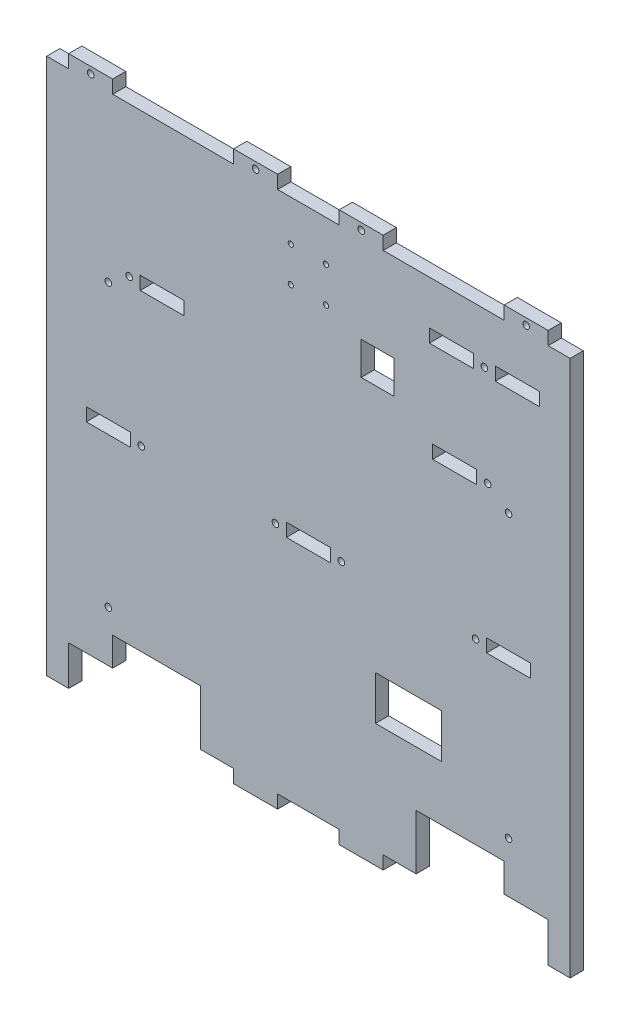
SolidWorks part; units mm, degrees
ref_plane "Plan de face" through (0, 0, 0) normal (0, 0, 1) x (1, 0, 0)
ref_plane "Plan de dessus" through (0, 0, 0) normal (0, 1, 0) x (1, 0, 0)
ref_plane "Plan de droite" through (0, 0, 0) normal (1, 0, 0) x (0, 0, -1)
sketch "Esquisse1" plane through (0, 0, 0) normal (0, 0, 1) x (1, 0, 0)
  line L0 (0, 139.6766) -> (0, -178.3461) construction
  line L1 (-109, 119) -> (109, 119)
  line L2 (-109, 119) -> (-109, -119)
  line L3 (-109, -119) -> (109, -119)
  line L4 (109, 119) -> (109, -119)
  line L5 (-101, -16) -> (-81, -16)
  line L6 (-101, -16) -> (-101, -10)
  line L7 (-101, -10) -> (-81, -10)
  line L8 (-81, -16) -> (-81, -10)
  line L9 (-10, -16) -> (10, -16)
  line L10 (-10, -16) -> (-10, -10)
  line L11 (-10, -10) -> (10, -10)
  line L12 (10, -16) -> (10, -10)
  line L13 (81, -16) -> (101, -16)
  line L14 (81, -16) -> (81, -10)
  line L15 (81, -10) -> (101, -10)
  line L16 (101, -16) -> (101, -10)
  line L17 (-76.5, 54) -> (-56.5, 54)
  line L18 (-76.5, 54) -> (-76.5, 48)
  line L19 (-76.5, 48) -> (-56.5, 48)
  line L20 (-56.5, 54) -> (-56.5, 48)
  line L21 (56.5, 54) -> (76.5, 54)
  line L22 (56.5, 54) -> (56.5, 48)
  line L23 (56.5, 48) -> (76.5, 48)
  line L24 (76.5, 54) -> (76.5, 48)
  line L25 (30.5, -69) -> (60.5, -69)
  line L26 (30.5, -69) -> (30.5, -49)
  line L27 (30.5, -49) -> (60.5, -49)
  line L28 (60.5, -69) -> (60.5, -49)
  line L30 (55, 99) -> (75, 99)
  line L31 (55, 99) -> (55, 93)
  line L32 (55, 93) -> (75, 93)
  line L33 (75, 99) -> (75, 93)
  line L34 (85, 99) -> (105, 99)
  line L35 (85, 99) -> (85, 93)
  line L36 (85, 93) -> (105, 93)
  line L37 (105, 99) -> (105, 93)
  line L38 (24, 64) -> (39, 64)
  line L39 (24, 64) -> (24, 79)
  line L40 (24, 79) -> (39, 79)
  line L41 (39, 64) -> (39, 79)
  dimension "D1" = 238
  dimension "D2" = 218
  dimension "D3" = 109
  dimension "D4" = 119
  dimension "D5" = 20
  dimension "D6" = 6
  dimension "D7" = 6
  dimension "D8" = 20
  dimension "D9" = 20
  dimension "D10" = 6
  dimension "D11" = 103
  dimension "D12" = 8
  dimension "D13" = 8
  dimension "D14" = 99
  dimension "D15" = 103
  dimension "D16" = 103
  dimension "D17" = 20
  dimension "D18" = 6
  dimension "D19" = 6
  dimension "D20" = 20
  dimension "D21" = 167
  dimension "D22" = 167
  dimension "D23" = 32.5
  dimension "D24" = 32.5
  dimension "D25" = 20
  dimension "D26" = 30
  dimension "D27" = 50
  dimension "D28" = 20.5
  dimension "D29" = 6
  dimension "D30" = 6
  dimension "D31" = 20
  dimension "D32" = 20
  dimension "D33" = 20
  dimension "D34" = 20
  dimension "D35" = 10
  dimension "D36" = 4
  dimension "D37" = 15
  dimension "D38" = 15
  dimension "D39" = 70
  dimension "D40" = 40
extrude "Boss.-Extru.1" add sketch "Esquisse1" along normal blind 6
sketch "Esquisse2" plane through (0, 0, 6) normal (0, 0, 1) x (1, 0, 0)
  line L0 (-109, -119) -> (109, -119) construction
  line L1 (-89, -119) -> (-49, -119)
  line L2 (-89, -119) -> (-89, -94)
  line L3 (-89, -94) -> (-49, -94)
  line L4 (-49, -119) -> (-49, -94)
  line L5 (-109, 119) -> (-109, -119) construction
  line L6 (49, -119) -> (89, -119)
  line L7 (49, -119) -> (49, -94)
  line L8 (49, -94) -> (89, -94)
  line L9 (89, -119) -> (89, -94)
  line L10 (109, -119) -> (109, 119) construction
  dimension "D1" = 40
  dimension "D2" = 20
  dimension "D3" = 40
  dimension "D4" = 20
  dimension "D5" = 25
  dimension "D6" = 25
extrude "Enlèv. mat.-Extru.1" cut sketch "Esquisse2" against normal blind 6
sketch "Esquisse3" plane through (0, 0, 6) normal (0, 0, 1) x (1, 0, 0)
  line L0 (0, 157.5653) -> (0, -190.6765) construction
  line L5 (-49, -119) -> (49, -119) construction
  line L6 (-34, -119) -> (-14, -119)
  line L7 (-34, -119) -> (-34, -125)
  line L8 (-34, -125) -> (-14, -125)
  line L9 (-14, -119) -> (-14, -125)
  line L10 (-49, -119) -> (-49, -94) construction
  line L15 (14, -119) -> (14, -125)
  line L16 (34, -125) -> (14, -125)
  line L17 (34, -119) -> (34, -125)
  line L18 (34, -119) -> (14, -119)
  line L19 (198.2674, 0) -> (-212.4835, 0) construction
  line L20 (0, -157.5653) -> (0, 190.6765) construction
  line L21 (34, 125) -> (14, 125)
  line L22 (14, 119) -> (14, 125)
  line L23 (89, 125) -> (109, 125)
  line L24 (89, 125) -> (89, 119)
  line L25 (89, 119) -> (109, 119)
  line L26 (109, 125) -> (109, 119)
  line L27 (-14, 119) -> (-14, 125)
  line L28 (-34, 125) -> (-14, 125)
  line L29 (-34, 119) -> (-34, 125)
  line L30 (-34, 119) -> (-14, 119)
  line L31 (-109, 125) -> (-109, 119)
  line L32 (-89, 119) -> (-109, 119)
  line L33 (-89, 125) -> (-89, 119)
  line L34 (-89, 125) -> (-109, 125)
  line L35 (34, 119) -> (14, 119)
  line L36 (34, 119) -> (34, 125)
  dimension "D2" = 20
  dimension "D3" = 6
  dimension "D4" = 15
extrude "Boss.-Extru.3" add sketch "Esquisse3" against normal blind 6
sketch "Esquisse4" plane through (0, 0, 6) normal (0, 0, 1) x (1, 0, 0)
  line L0 (-111.0944, 51) -> (126.4062, 51) construction
  line L1 (116.6655, -13) -> (-122.9189, -13) construction
  line L2 (76.5, 48) -> (76.5, 54) construction
  line L3 (0, 153.5677) -> (0, -173.1111) construction
  line L4 (45.0686, 96) -> (109.1297, 96) construction
  line L5 (81, -10) -> (81, -16) construction
  line L6 (10, -16) -> (10, -10) construction
  line L7 (-10, -10) -> (-10, -16) construction
  line L8 (75, 93) -> (75, 99) construction
  line L9 (-114.2336, 122) -> (-6.2018, 122) construction
  line L10 (-56.5, 54) -> (-76.5, 54) construction
  line L11 (-89, 125) -> (-109, 125) construction
  line L12 (-34, 125) -> (-34, 119) construction
  line L13 (55, 93) -> (75, 93) construction
  line L14 (-89, 119) -> (-89, 125) construction
  line L15 (-81, -10) -> (-101, -10) construction
  line L16 (-91, 66.959) -> (-91, -106.1689) construction
  line L17 (-49, -94) -> (-89, -94) construction
  line L18 (-109, 125) -> (-109, -119) construction
  circle A0 centre (-15, -13) radius 1.5
  circle A1 centre (-76, -13) radius 1.5
  circle A2 centre (80, 96) radius 1.5
  circle A3 centre (81.5, 51) radius 1.5
  circle A4 centre (76, -13) radius 1.5
  circle A5 centre (15, -13) radius 1.5
  circle A6 centre (-81.5, 51) radius 1.5
  circle A7 centre (-99, 122) radius 1.5
  circle A8 centre (-24, 122) radius 1.5
  circle A9 centre (24, 122) radius 1.5
  circle A10 centre (99, 122) radius 1.5
  circle A11 centre (-91, -84) radius 1.5
  circle A12 centre (-91, 44) radius 1.5
  circle A13 centre (91, -84) radius 1.5
  circle A14 centre (91, 44) radius 1.5
  dimension "D2" = 5
  dimension "D3" = 3
  dimension "D4" = 3
  dimension "D5" = 5
  dimension "D6" = 5
  dimension "D7" = 3
  dimension "D8" = 3
  dimension "D9" = 3
  dimension "D10" = 5
  dimension "D11" = 3
  dimension "D12" = 5
  dimension "D13" = 3
  dimension "D15" = 3
  dimension "D16" = 3
  dimension "D17" = 10
  dimension "D18" = 10
  dimension "D19" = 3
  dimension "D20" = 3
  dimension "D21" = 3
  dimension "D22" = 128
  dimension "D14" = 3
  dimension "D23" = 10
  dimension "D24" = 18
extrude "Enlèv. mat.-Extru.2" cut sketch "Esquisse4" against normal blind 6
sketch "Esquisse5" plane through (0, 0, 6) normal (0, 0, 1) x (1, 0, 0)
  line L0 (-109, 119) -> (-109, -125)
  line L1 (-109, 119) -> (-119, 119)
  line L2 (-109, -125) -> (-119, -125)
  line L3 (-119, 119) -> (-119, -125)
  line L5 (109, -125) -> (109, 119)
  line L6 (109, -125) -> (119, -125)
  line L7 (109, 119) -> (119, 119)
  line L8 (119, -125) -> (119, 119)
  line L11 (109, 125) -> (89, 125) construction
  line L12 (-89, 125) -> (-109, 125) construction
  dimension "D1" = 10
  dimension "D2" = 10
  dimension "D3" = 244
  dimension "D4" = 244
  dimension "D5" = 6
  dimension "D6" = 6
extrude "Boss.-Extru.4" add sketch "Esquisse5" against normal blind 6
sketch "Esquisse6" plane through (0, 0, 6) normal (0, 0, 1) x (1, 0, 0)
  line L0 (0, 108.4917) -> (0, -172.5759) construction
  line L1 (89, -119) -> (109, -119)
  line L2 (89, -119) -> (89, -107)
  line L3 (89, -107) -> (109, -107)
  line L4 (109, -119) -> (109, -107)
  line L5 (-109, -119) -> (-109, -107)
  line L6 (-89, -107) -> (-109, -107)
  line L7 (-89, -119) -> (-89, -107)
  line L8 (-89, -119) -> (-109, -119)
  dimension "D1" = 12
  dimension "D2" = 20
extrude "Enlèv. mat.-Extru.3" cut sketch "Esquisse6" against normal blind 6
sketch "Esquisse7" plane through (0, 0, 6) normal (0, 0, 1) x (1, 0, 0)
  line L0 (14, 119) -> (-14, 119) construction
  line L1 (14, 125) -> (14, 119) construction
  circle A0 centre (-8, 100.5) radius 1.175
  circle A1 centre (8, 100.5) radius 1.175
  circle A2 centre (-8, 84.5) radius 1.175
  circle A3 centre (8, 84.5) radius 1.175
  dimension "D1" = 16
  dimension "D7" = 2.35
  dimension "D8" = 2.35
  dimension "D9" = 2.35
  dimension "D10" = 2.35
  dimension "D2" = 16
  dimension "D3" = 16
  dimension "D4" = 16
  dimension "D5" = 18.5
  dimension "D6" = 6
  dimension "D11" = 18.5
extrude "Enlèv. mat.-Extru.4" cut sketch "Esquisse7" against normal through all
equation "\"D3@Esquisse1\"=\"D2@Esquisse1\"/2"
equation "\"D4@Esquisse1\"=\"D1@Esquisse1\"/2"
